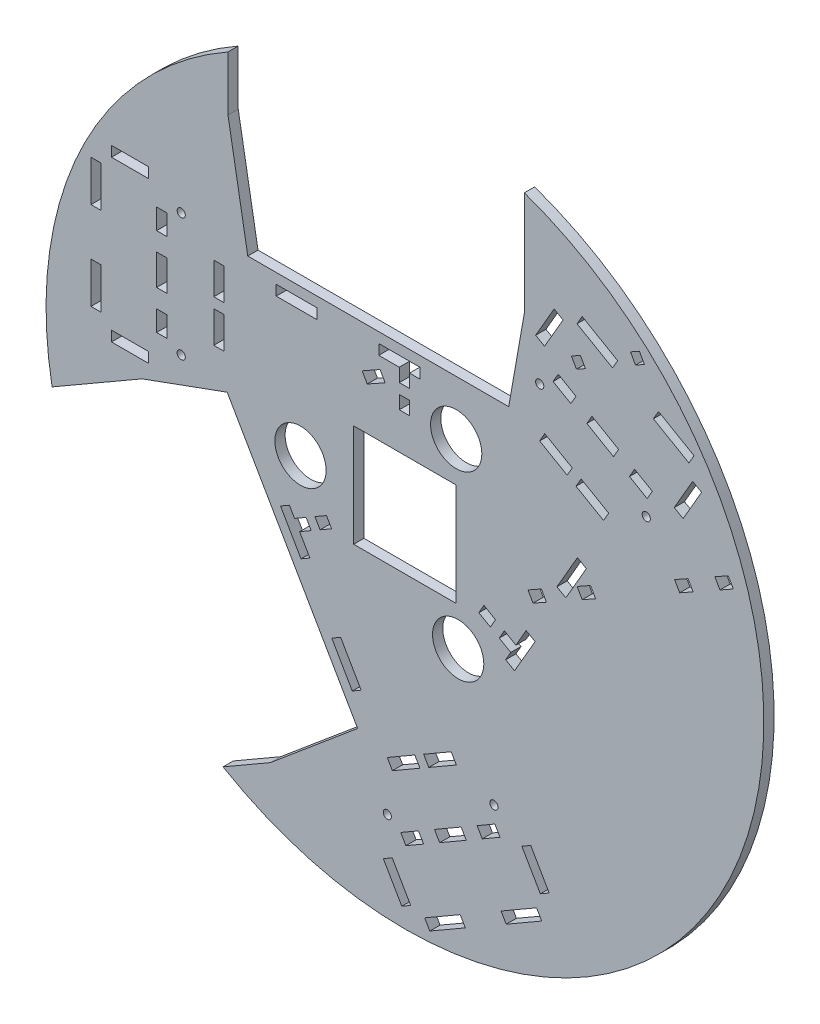
SolidWorks part; units mm, degrees
material "Balsa"
ref_plane "Plan de face" through (0, 0, 0) normal (0, 0, 1) x (1, 0, 0)
ref_plane "Plan de dessus" through (0, 0, 0) normal (0, 1, 0) x (1, 0, 0)
ref_plane "Plan de droite" through (0, 0, 0) normal (1, 0, 0) x (0, 0, -1)
sketch "Esquisse1" plane through (0, 0, 0) normal (0, 0, 1) x (1, 0, 0)
  circle A0 centre (148.0804, -12.1102) radius 175
  dimension "D1" = 350
extrude "Boss.-Extru.1" add sketch "Esquisse1" along normal blind 5
sketch "Esquisse2" plane through (0, 0, 5) normal (0, 0, 1) x (1, 0, 0)
  line L0 (135.3118, 53.7774) -> (135.3118, 48.7774)
  line L1 (5, 72.2774) -> (23, 72.2774)
  line L2 (5, 72.2774) -> (5, 67.2774)
  line L3 (5, 67.2774) -> (23, 67.2774)
  line L4 (23, 72.2774) -> (23, 67.2774)
  line L5 (-5, 62.2774) -> (0, 62.2774)
  line L6 (-5, 62.2774) -> (-5, 42.2774)
  line L7 (-5, 42.2774) -> (0, 42.2774)
  line L8 (0, 62.2774) -> (0, 42.2774)
  line L9 (-5, 19.2774) -> (0, 19.2774)
  line L10 (-5, 19.2774) -> (-5, -0.7226)
  line L11 (-5, -0.7226) -> (0, -0.7226)
  line L12 (0, 19.2774) -> (0, -0.7226)
  line L13 (5, -5.7226) -> (23, -5.7226)
  line L14 (5, -5.7226) -> (5, -10.7226)
  line L15 (5, -10.7226) -> (23, -10.7226)
  line L16 (23, -5.7226) -> (23, -10.7226)
  line L17 (27, 14.2774) -> (32, 14.2774)
  line L18 (27, 14.2774) -> (27, 4.2774)
  line L19 (27, 4.2774) -> (32, 4.2774)
  line L20 (32, 14.2774) -> (32, 4.2774)
  line L21 (27, 38.2774) -> (32, 38.2774)
  line L22 (27, 38.2774) -> (27, 23.2774)
  line L23 (27, 23.2774) -> (32, 23.2774)
  line L24 (32, 38.2774) -> (32, 23.2774)
  line L25 (27, 57.2774) -> (32, 57.2774)
  line L26 (27, 57.2774) -> (27, 47.2774)
  line L27 (27, 47.2774) -> (32, 47.2774)
  line L28 (32, 57.2774) -> (32, 47.2774)
  line L29 (54.86, 48.7774) -> (59.86, 48.7774)
  line L30 (54.86, 48.7774) -> (54.86, 33.2774)
  line L31 (54.86, 33.2774) -> (59.86, 33.2774)
  line L32 (59.86, 48.7774) -> (59.86, 33.2774)
  line L33 (54.86, 28.2774) -> (59.86, 28.2774)
  line L34 (54.86, 28.2774) -> (54.86, 12.7774)
  line L35 (54.86, 12.7774) -> (59.86, 12.7774)
  line L36 (59.86, 28.2774) -> (59.86, 12.7774)
  line L37 (85.3118, 53.7774) -> (105.3118, 53.7774)
  line L38 (85.3118, 53.7774) -> (85.3118, 48.7774)
  line L39 (85.3118, 48.7774) -> (105.3118, 48.7774)
  line L40 (105.3118, 53.7774) -> (105.3118, 48.7774)
  line L41 (145.3118, 37.2774) -> (150.3118, 37.2774)
  line L42 (145.3118, 37.2774) -> (145.3118, 30.7774)
  line L43 (145.3118, 30.7774) -> (150.3118, 30.7774)
  line L44 (150.3118, 37.2774) -> (150.3118, 30.7774)
  line L45 (135.3118, 48.7774) -> (145.3118, 48.7774)
  line L46 (155.3118, 48.7774) -> (135.3118, 48.7774) construction
  line L47 (145.3118, 48.7774) -> (145.3118, 42.2774)
  line L48 (145.3118, 42.2774) -> (150.3118, 42.2774)
  line L49 (150.3118, 42.2774) -> (150.3118, 48.7774)
  line L50 (150.3118, 48.7774) -> (155.3118, 48.7774)
  line L51 (155.3118, 48.7774) -> (155.3118, 53.7774)
  line L52 (155.3118, 53.7774) -> (135.3118, 53.7774)
  line L53 (292.7025, 69.6073) -> (283.7025, 54.0188)
  line L54 (292.7025, 69.6073) -> (288.3723, 72.1073)
  line L55 (288.3723, 72.1073) -> (279.3723, 56.5188)
  line L56 (283.7025, 54.0188) -> (279.3723, 56.5188)
  line L57 (289.0422, 83.2676) -> (286.5422, 78.9374)
  line L58 (289.0422, 83.2676) -> (271.7217, 93.2676)
  line L59 (271.7217, 93.2676) -> (269.2217, 88.9374)
  line L60 (286.5422, 78.9374) -> (269.2217, 88.9374)
  line L61 (251.8031, 104.7676) -> (249.3031, 100.4374)
  line L62 (251.8031, 104.7676) -> (234.4826, 114.7676)
  line L63 (234.4826, 114.7676) -> (231.9826, 110.4374)
  line L64 (249.3031, 100.4374) -> (231.9826, 110.4374)
  line L65 (225.1525, 108.6073) -> (216.1525, 93.0188)
  line L66 (225.1525, 108.6073) -> (220.8223, 111.1073)
  line L67 (220.8223, 111.1073) -> (211.8223, 95.5188)
  line L68 (216.1525, 93.0188) -> (211.8223, 95.5188)
  line L69 (231.473, 79.5547) -> (228.973, 75.2246)
  line L70 (231.473, 79.5547) -> (222.8127, 84.5547)
  line L71 (222.8127, 84.5547) -> (220.3127, 80.2246)
  line L72 (228.973, 75.2246) -> (220.3127, 80.2246)
  line L73 (252.2576, 67.5547) -> (249.7576, 63.2246)
  line L74 (252.2576, 67.5547) -> (239.2672, 75.0547)
  line L75 (239.2672, 75.0547) -> (236.7672, 70.7246)
  line L76 (249.7576, 63.2246) -> (236.7672, 70.7246)
  line L77 (268.7121, 58.0547) -> (266.2121, 53.7246)
  line L78 (268.7121, 58.0547) -> (260.0518, 63.0547)
  line L79 (260.0518, 63.0547) -> (257.5518, 58.7246)
  line L80 (266.2121, 53.7246) -> (257.5518, 58.7246)
  line L81 (247.4209, 38.1773) -> (244.9209, 33.8472)
  line L82 (247.4209, 38.1773) -> (233.9975, 45.9273)
  line L83 (233.9975, 45.9273) -> (231.4975, 41.5972)
  line L84 (244.9209, 33.8472) -> (231.4975, 41.5972)
  line L85 (229.6673, 48.4273) -> (227.1673, 44.0972)
  line L86 (229.6673, 48.4273) -> (216.2439, 56.1773)
  line L87 (216.2439, 56.1773) -> (213.7439, 51.8472)
  line L88 (227.1673, 44.0972) -> (213.7439, 51.8472)
  line L89 (211.5251, -33.996) -> (207.195, -31.496)
  line L90 (236.5251, 9.3053) -> (226.5251, -8.0153)
  line L91 (236.5251, 9.3053) -> (232.195, 11.8053)
  line L92 (232.195, 11.8053) -> (222.195, -5.5153)
  line L93 (226.5251, -8.0153) -> (222.195, -5.5153)
  line L94 (192.2357, -34.4063) -> (189.7357, -38.7364)
  line L95 (192.2357, -34.4063) -> (186.6065, -31.1563)
  line L96 (186.6065, -31.1563) -> (184.1065, -35.4864)
  line L97 (189.7357, -38.7364) -> (184.1065, -35.4864)
  line L98 (207.195, -31.496) -> (202.195, -40.1563)
  line L99 (202.195, -40.1563) -> (196.5658, -36.9063)
  line L100 (196.5658, -36.9063) -> (194.0658, -41.2364)
  line L101 (194.0658, -41.2364) -> (199.695, -44.4864)
  line L102 (199.695, -44.4864) -> (197.195, -48.8165)
  line L103 (197.195, -48.8165) -> (201.5251, -51.3165)
  line L104 (201.5251, -51.3165) -> (211.5251, -33.996)
  line L105 (146.5388, -178.2153) -> (137.5388, -162.6268)
  line L106 (146.5388, -178.2153) -> (150.869, -175.7153)
  line L107 (150.869, -175.7153) -> (141.869, -160.1268)
  line L108 (137.5388, -162.6268) -> (141.869, -160.1268)
  line L109 (160.1991, -181.8755) -> (157.6991, -177.5454)
  line L110 (160.1991, -181.8755) -> (177.5196, -171.8755)
  line L111 (177.5196, -171.8755) -> (175.0196, -167.5454)
  line L112 (157.6991, -177.5454) -> (175.0196, -167.5454)
  line L113 (197.4382, -160.3755) -> (194.9382, -156.0454)
  line L114 (197.4382, -160.3755) -> (214.7587, -150.3755)
  line L115 (214.7587, -150.3755) -> (212.2587, -146.0454)
  line L116 (194.9382, -156.0454) -> (212.2587, -146.0454)
  line L117 (214.0888, -139.2153) -> (205.0888, -123.6268)
  line L118 (214.0888, -139.2153) -> (218.4189, -136.7153)
  line L119 (218.4189, -136.7153) -> (209.4189, -121.1268)
  line L120 (205.0888, -123.6268) -> (209.4189, -121.1268)
  line L121 (185.7683, -130.1627) -> (183.2683, -125.8326)
  line L122 (185.7683, -130.1627) -> (194.4286, -125.1627)
  line L123 (194.4286, -125.1627) -> (191.9286, -120.8326)
  line L124 (183.2683, -125.8326) -> (191.9286, -120.8326)
  line L125 (164.9837, -142.1627) -> (162.4837, -137.8326)
  line L126 (164.9837, -142.1627) -> (177.9741, -134.6627)
  line L127 (177.9741, -134.6627) -> (175.4741, -130.3326)
  line L128 (162.4837, -137.8326) -> (175.4741, -130.3326)
  line L129 (148.5292, -151.6627) -> (146.0292, -147.3326)
  line L130 (148.5292, -151.6627) -> (157.1895, -146.6627)
  line L131 (157.1895, -146.6627) -> (154.6895, -142.3326)
  line L132 (146.0292, -147.3326) -> (154.6895, -142.3326)
  line L133 (141.9604, -123.2852) -> (139.4604, -118.9551)
  line L134 (141.9604, -123.2852) -> (155.3838, -115.5352)
  line L135 (155.3838, -115.5352) -> (152.8838, -111.2051)
  line L136 (139.4604, -118.9551) -> (152.8838, -111.2051)
  line L137 (159.7139, -113.0352) -> (157.2139, -108.7051)
  line L138 (159.7139, -113.0352) -> (173.1373, -105.2852)
  line L139 (173.1373, -105.2852) -> (170.6373, -100.9551)
  line L140 (157.2139, -108.7051) -> (170.6373, -100.9551)
  line L141 (97.4044, -56.1119) -> (101.7345, -53.6119)
  line L142 (122.4044, -99.4132) -> (112.4044, -82.0927)
  line L143 (122.4044, -99.4132) -> (126.7345, -96.9132)
  line L144 (126.7345, -96.9132) -> (116.7345, -79.5927)
  line L145 (112.4044, -82.0927) -> (116.7345, -79.5927)
  line L146 (106.6938, -39.2017) -> (104.1938, -34.8716)
  line L147 (106.6938, -39.2017) -> (112.323, -35.9517)
  line L148 (112.323, -35.9517) -> (109.823, -31.6216)
  line L149 (104.1938, -34.8716) -> (109.823, -31.6216)
  line L150 (101.7345, -53.6119) -> (96.7345, -44.9517)
  line L151 (96.7345, -44.9517) -> (102.3637, -41.7017)
  line L152 (102.3637, -41.7017) -> (99.8637, -37.3716)
  line L153 (99.8637, -37.3716) -> (94.2345, -40.6216)
  line L154 (94.2345, -40.6216) -> (91.7345, -36.2914)
  line L155 (91.7345, -36.2914) -> (87.4044, -38.7914)
  line L156 (87.4044, -38.7914) -> (97.4044, -56.1119)
  line L157 (135.3118, 53.7774) -> (135.3118, 48.7774) construction
  line L158 (105.3118, 53.7774) -> (135.3118, 53.7774) construction
  point P83 (148.0804, -12.1102)
  point P192 (148.0804, -12.1102)
  point P193 (148.0804, -12.1102)
  dimension "D1" = 3
extrude "Enlèv. mat.-Extru.1" cut sketch "Esquisse2" against normal blind 5
sketch "Esquisse6" plane through (0, 0, 5) normal (0, 0, 1) x (1, 0, 0)
  line L0 (93.9998, -7.2151) -> (100.2998, -18.127) construction
  line L1 (206.3213, 102.2219) -> (206.3213, 185.5637)
  line L2 (123.0804, -37.1102) -> (173.0804, -37.1102)
  line L3 (123.0804, -37.1102) -> (123.0804, 12.8898)
  line L4 (123.0804, 12.8898) -> (173.0804, 12.8898)
  line L5 (173.0804, -37.1102) -> (173.0804, 12.8898)
  line L6 (123.0804, -37.1102) -> (173.0804, 12.8898) construction
  line L7 (123.0804, 12.8898) -> (173.0804, -37.1102) construction
  line L8 (206.3213, 185.5637) -> (61.7972, 185.5637)
  line L9 (61.7972, 113.4862) -> (71.4438, 58.7774)
  line L10 (71.4438, 58.7774) -> (198.6608, 58.7774)
  line L11 (198.6608, 58.7774) -> (206.3213, 102.2219)
  line L12 (61.7972, 185.5637) -> (61.7972, 113.4862)
  line L13 (19.9456, -18.8381) -> (-52.2306, -60.5091)
  line L14 (-52.2306, -60.5091) -> (20.0314, -185.6706)
  line L15 (82.4524, -149.6318) -> (125.0083, -113.9232)
  line L16 (125.0083, -113.9232) -> (61.3998, -3.7501)
  line L17 (61.3998, -3.7501) -> (19.9456, -18.8381)
  line L18 (20.0314, -185.6706) -> (82.4524, -149.6318)
  line L19 (87.4044, -38.7914) -> (97.4044, -56.1119) construction
  circle A0 centre (173.06, 32.2774) radius 12.5
  circle A1 centre (174.0314, -55.9369) radius 12.5
  circle A2 centre (97.1498, -12.671) radius 12.5
  point P2 (148.0804, -12.1102)
  point P8 (148.0804, -12.1102)
  point P10 (148.0804, -12.1102)
  point P35 (148.0804, -12.1102)
  dimension "D2" = 25
  dimension "D3" = 50
  dimension "D4" = 50
  dimension "D5" = 70.8876
  dimension "D6" = 50.5804
  dimension "D7" = 127.217
  dimension "D8" = 100
  dimension "D9" = 100
  dimension "D10" = 54.7088
  dimension "D11" = 43.4444
  dimension "D1" = 3
  dimension "D12" = 2
extrude "Enlèv. mat.-Extru.6" cut sketch "Esquisse6" against normal blind 5
hole_wizard "Trous de centrage Ø4.0mm1" positions "Esquisse7" profile "Esquisse8" hole size "Ø4.0" standard "Ansi Metric" end condition through all
sketch "Esquisse7" plane through (148.0804, -12.1102, -78) normal (0, 0, -1) x (1, 0, 0)
  point P0 (65.7012, -88.0226)
  point P3 (117.6627, -58.0226)
  point P6 (-109.0804, -72.8876)
  point P9 (-109.0804, -12.8876)
  point P12 (-8.5823, 130.9102)
  point P15 (43.3792, 100.9102)
sketch "Esquisse8" plane through (213.7816, 75.9124, -78) normal (1, 0, 0) x (0, 1, 0)
  line L0 (0, 0) -> (0, 83)
  line L1 (0, 83) -> (2, 83)
  line L2 (2, 83) -> (2, 0)
  line L3 (2, 0) -> (0, 0)
  line L4 (0, -6.35) -> (0, 107.95) construction
  dimension "Diamètre du perçage jusqu'au prochain" = 4
  dimension "Profondeur du perçage jusqu'au prochain" = 83
sketch "Esquisse9" plane through (0, 0, 5) normal (0, 0, 1) x (1, 0, 0)
  line L0 (301.6473, 32.8747) -> (299.2005, 37.2351)
  line L1 (301.6473, 32.8747) -> (308.1879, 36.5449)
  line L2 (299.2005, 37.2351) -> (305.7411, 40.9053)
  line L3 (308.1879, 36.5449) -> (305.7411, 40.9053)
  line L4 (282.0254, 21.8642) -> (279.5786, 26.2246)
  line L5 (282.0254, 21.8642) -> (288.566, 25.5344)
  line L6 (279.5786, 26.2246) -> (286.1192, 29.8948)
  line L7 (288.566, 25.5344) -> (286.1192, 29.8948)
  line L8 (241.0375, -1.1356) -> (238.5907, 3.2248)
  line L9 (241.0375, -1.1356) -> (234.4969, -4.8058)
  line L10 (238.5907, 3.2248) -> (232.0501, -0.4454)
  line L11 (234.4969, -4.8058) -> (232.0501, -0.4454)
  line L12 (214.6084, -10.2326) -> (217.0552, -14.593)
  line L13 (214.6084, -10.2326) -> (208.0678, -13.9027)
  line L14 (217.0552, -14.593) -> (210.5146, -18.2632)
  line L15 (208.0678, -13.9027) -> (210.5146, -18.2632)
  line L16 (217.0552, -14.593) -> (234.4969, -4.8058) construction
  line L17 (214.6084, -10.2326) -> (217.0552, -14.593) construction
  line L18 (264.8483, 109.6933) -> (260.4879, 107.2465)
  line L19 (264.8483, 109.6933) -> (262.4015, 114.0537)
  line L20 (260.4879, 107.2465) -> (258.0411, 111.6069)
  line L21 (262.4015, 114.0537) -> (258.0411, 111.6069)
  line L22 (236.0696, 93.5445) -> (231.7091, 91.0977)
  line L23 (236.0696, 93.5445) -> (233.6228, 97.9049)
  line L24 (231.7091, 91.0977) -> (229.2624, 95.4581)
  line L25 (233.6228, 97.9049) -> (229.2624, 95.4581)
  line L26 (138.3962, 38.7364) -> (129.6754, 33.8428)
  line L27 (138.3962, 38.7364) -> (135.9495, 43.0968)
  line L28 (129.6754, 33.8428) -> (127.2286, 38.2032)
  line L29 (135.9495, 43.0968) -> (127.2286, 38.2032)
  line L30 (264.8483, 109.6933) -> (129.6754, 33.8428) construction
  line L31 (301.6473, 32.8747) -> (217.0552, -14.593) construction
  dimension "D1" = 10
  dimension "D2" = 5
  dimension "D3" = 7.5
  dimension "D4" = 7.5
  dimension "D5" = 7.5
  dimension "D6" = 7.5
extrude "Enlèv. mat.-Extru.7" cut sketch "Esquisse9" against normal blind 10
